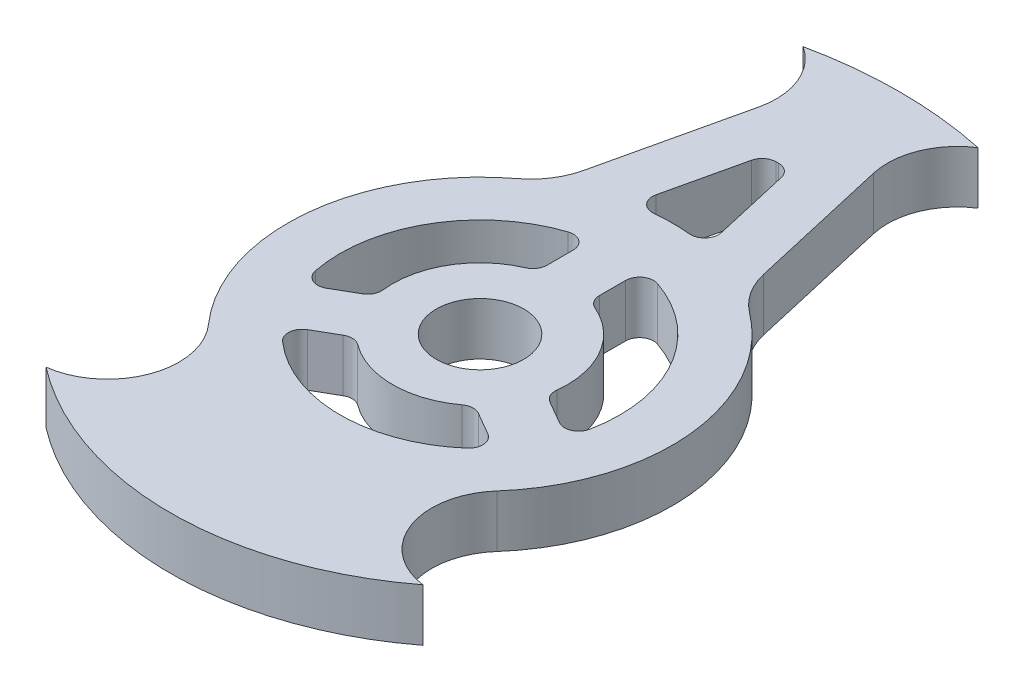
SolidWorks part; units mm, degrees
material "AISI Type A2 Tool Steel"
ref_plane "Front Plane" through (0, 0, 0) normal (0, 0, 1) x (1, 0, 0)
ref_plane "Top Plane" through (0, 0, 0) normal (0, 1, 0) x (1, 0, 0)
ref_plane "Right Plane" through (0, 0, 0) normal (1, 0, 0) x (0, 0, -1)
other "Center of Mass"
other "Bounding Box"
ref_plane "Default Plane" through (-8.9266, -12.7485, 0) normal (-0.1736, 0.9848, 0) x (0.9848, 0.1736, 0)
sketch "Sketch1" plane through (0, 0, 0) normal (0, 1, 0) x (1, 0, 0)
  circle A0 centre (0, 0) radius 7.9375
  circle A1 centre (0, 0) radius 34.925
  circle A2 centre (0, 0) radius 76.2 construction
  dimension "D1" = 15.875
  dimension "D2" = 152.4
  dimension "D3" = 69.85
extrude "Boss-Extrude1" add sketch "Sketch1" along normal mid plane 9.525
sketch "Sketch2" plane through (0, 4.7625, 0) normal (0, 1, 0) x (1, 0, 0)
  line L0 (-17.4625, 30.2459) -> (-10.408, 61.0378)
  line L1 (17.4625, 30.2459) -> (10.408, 61.0378)
  line L2 (-15.875, 74.528) -> (15.875, 74.528) construction
  line L3 (0, 0) -> (0, 76.2) construction
  line L4 (0, 0) -> (15.875, 74.528) construction
  line L5 (15.875, 74.528) -> (-74.528, 15.875) construction
  line L6 (-17.4625, 30.2459) -> (0, 30.2459) construction
  line L7 (0, 30.2459) -> (17.4625, 30.2459) construction
  circle A0 centre (0, 0) radius 34.925 construction
  circle A1 centre (0, 0) radius 76.2 construction
  arc A2 (-15.875, 74.528) -> (15.875, 74.528) centre (0, 0) cw
  arc A3 (10.408, 61.0378) -> (15.875, 74.528) centre (22.7873, 63.8739) cw
  arc A4 (17.4625, 30.2459) -> (-17.4625, 30.2459) centre (0, 0) ccw
  circle A5 centre (0, 0) radius 34.925 construction
  arc A6 (-10.408, 61.0378) -> (-15.875, 74.528) centre (-22.7873, 63.8739) ccw
  dimension "D1" = 45
  dimension "D3" = 12.7
  dimension "D2" = 31.75
  dimension "D4" = 34.925
extrude "Boss-Extrude2" add sketch "Sketch2" against normal up to surface (9.525 mm away) up to face at (0, -4.7625, 34.925)
sketch "Sketch3" plane through (0, 4.7625, 0) normal (0, 1, 0) x (1, 0, 0)
  line L0 (-34.2109, -44.5845) -> (0, 0) construction
  line L1 (0, 0) -> (34.2109, -44.5845) construction
  line L2 (0, 0) -> (0, -76.2) construction
  line L3 (0, 0) -> (0, -76.2) construction
  line L4 (-34.2109, -44.5845) -> (69.6487, -30.9111) construction
  arc A0 (-34.2109, -44.5845) -> (34.2109, -44.5845) centre (0, 0) ccw
  arc A1 (-34.2109, -44.5845) -> (-26.176, -23.1208) centre (-35.9052, -31.7144) ccw
  circle A2 centre (0, 0) radius 34.925 construction
  arc A3 (34.2109, -44.5845) -> (26.176, -23.1208) centre (35.9052, -31.7144) cw
  arc A4 (-26.176, -23.1208) -> (26.176, -23.1208) centre (0, 0) ccw
  circle A5 centre (0, 0) radius 76.2 construction
  point P6 (0, -56.1975)
  dimension "D1" = 56.1975
  dimension "D2" = 75
  dimension "D4" = 45
extrude "Boss-Extrude3" add sketch "Sketch3" against normal up to surface (9.525 mm away) up to face at (0, -4.7625, -44.9744)
sketch "Sketch4" plane through (0, 4.7625, 0) normal (0, 1, 0) x (1, 0, 0)
  line L0 (15.4962, -3.4474) -> (23.9882, -8.3503)
  line L1 (4.7625, 15.1438) -> (4.7625, 24.9495)
  line L2 (0, 0) -> (30.2459, -17.4625) construction
  line L3 (0, 0) -> (0, 34.925) construction
  line L4 (4.7625, 24.9495) -> (0, 24.9495) construction
  line L5 (23.9882, -8.3503) -> (21.6069, -12.4748) construction
  arc A0 (4.7625, 15.1438) -> (15.4962, -3.4474) centre (0, 0) cw
  arc A1 (4.7625, 24.9495) -> (23.9882, -8.3503) centre (0, 0) cw
  circle A2 centre (0, 0) radius 34.925 construction
  dimension "D2" = 9.525
  dimension "D3" = 15.875
  dimension "D1" = 4.7625
  dimension "D4" = 120
extrude "Cut-Extrude1" cut sketch "Sketch4" against normal through all
fillet "Fillet1" radius 2.54 4 edges at (23.9882, 0, 8.3503) (15.4962, 0, 3.4474) (4.7625, 0, -15.1438) (4.7625, 0, -24.9495)
pattern_circular "CirPattern1" count 3 over 360 about axis through (0, 4.7625, 0) along (0, -1, 0) of "Cut-Extrude1", "Fillet1" reverse direction yes
sketch "Sketch5" plane through (0, 4.7625, 0) normal (0, 1, 0) x (1, 0, 0)
  line L1 (-6.7705, 34.2624) -> (-2.2653, 53.9274)
  line L2 (2.2653, 53.9274) -> (6.7705, 34.2624)
  line L3 (17.4625, 30.2459) -> (10.408, 61.0378) construction
  line L4 (-10.408, 61.0378) -> (-17.4625, 30.2459) construction
  line L5 (-2.2653, 53.9274) -> (-11.5497, 56.0545) construction
  line L6 (4.5179, 44.0949) -> (13.8024, 46.222) construction
  arc A2 (-6.7705, 34.2624) -> (6.7705, 34.2624) centre (0, 0) cw
  arc A3 (2.2653, 53.9274) -> (-2.2653, 53.9274) centre (0, 0) ccw
  arc A4 (26.176, -23.1208) -> (17.4625, 30.2459) centre (0, 0) ccw construction
  dimension "D1" = 9.525
  dimension "D2" = 19.05
extrude "Cut-Extrude2" cut sketch "Sketch5" against normal through all
fillet "Fillet2" radius 2.54 4 edges at (6.7705, 0, -34.2624) (-6.7705, 0, -34.2624) (-2.2653, 0, -53.9274) (2.2653, 0, -53.9274)
fillet "Fillet3" radius 12.7 2 edges at (-17.4625, 0, -30.2459) (17.4625, 0, -30.2459)
